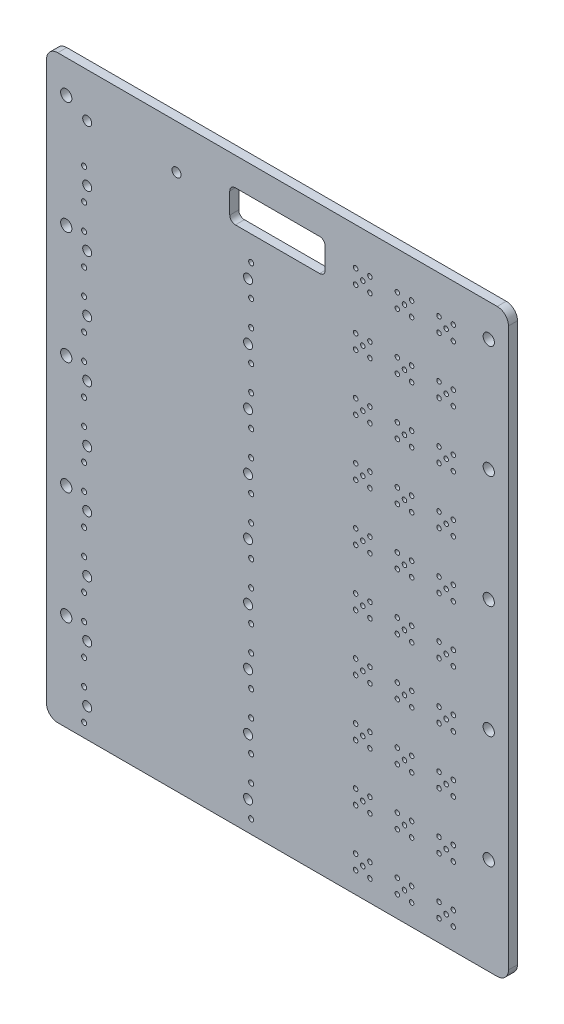
SolidWorks part; units mm, degrees
ref_plane "Front Plane" through (0, 0, 0) normal (0, 0, 1) x (1, 0, 0)
ref_plane "Top Plane" through (0, 0, 0) normal (0, 1, 0) x (1, 0, 0)
ref_plane "Right Plane" through (0, 0, 0) normal (1, 0, 0) x (0, 0, -1)
ref_plane "Plane4" through (0, 0, 0) normal (0, 0, -1) x (-1, 0, 0)
sketch "Sketch1" plane through (0, 0, 0) normal (0, 0, -1) x (-1, 0, 0)
  line L0 (7.475, 96.3) -> (-7.475, 96.3)
  line L1 (-8.475, 97.3) -> (-8.475, 101)
  line L2 (-7.475, 102) -> (7.475, 102)
  line L3 (8.475, 101) -> (8.475, 97.3)
  line L4 (39, 107) -> (-39, 107)
  line L5 (-41, 105) -> (-41, -105)
  line L6 (-39, -107) -> (39, -107)
  line L7 (41, -105) -> (41, 105)
  line L8 (8.475, -101) -> (8.475, -97.3)
  line L9 (-7.475, -102) -> (7.475, -102)
  line L10 (-8.475, -97.3) -> (-8.475, -101)
  line L11 (7.475, -96.3) -> (-7.475, -96.3)
  line L12 (41, -105) -> (41, -107) construction
  line L13 (41, -107) -> (39, -107) construction
  line L14 (41, 0) -> (-41, 0) construction
  line L15 (0, 107) -> (0, -107) construction
  arc A0 (8.475, 97.3) -> (7.475, 96.3) centre (7.475, 97.3) cw
  arc A1 (-7.475, 96.3) -> (-8.475, 97.3) centre (-7.475, 97.3) cw
  arc A2 (-8.475, 101) -> (-7.475, 102) centre (-7.475, 101) cw
  arc A3 (7.475, 102) -> (8.475, 101) centre (7.475, 101) cw
  circle A4 centre (34.325, -40.5) radius 0.45
  circle A5 centre (5.225, -43.25) radius 0.8
  circle A6 centre (-37.5, 21.2) radius 1
  circle A7 centre (5.225, -33.25) radius 0.8
  circle A8 centre (34.325, 46.5) radius 0.45
  circle A9 centre (33.775, -53.25) radius 0.8
  circle A10 centre (34.325, 82) radius 0.45
  circle A11 centre (4.675, 66.5) radius 0.45
  circle A12 centre (33.775, 19.25) radius 0.8
  circle A13 centre (4.675, -0.5) radius 0.45
  circle A14 centre (34.325, 26.5) radius 0.45
  circle A15 centre (5.225, -73.25) radius 0.8
  circle A16 centre (34.325, -66) radius 0.45
  circle A17 centre (5.225, 29.25) radius 0.8
  circle A18 centre (34.325, -80.5) radius 0.45
  circle A19 centre (34.325, 36.5) radius 0.45
  circle A20 centre (4.675, 22) radius 0.45
  circle A21 centre (33.775, -23.25) radius 0.8
  circle A22 centre (5.225, 19.25) radius 0.8
  circle A23 centre (33.775, -13.25) radius 0.8
  circle A24 centre (4.675, -10.5) radius 0.45
  circle A25 centre (34.325, 52) radius 0.45
  circle A26 centre (5.225, 89.25) radius 0.8
  circle A27 centre (5.225, -53.25) radius 0.8
  circle A28 centre (34.325, -70.5) radius 0.45
  circle A29 centre (34.325, -36) radius 0.45
  circle A30 centre (5.225, 59.25) radius 0.8
  circle A31 centre (33.775, 59.25) radius 0.8
  circle A32 centre (34.325, 32) radius 0.45
  circle A33 centre (33.775, -73.25) radius 0.8
  circle A34 centre (4.675, 46.5) radius 0.45
  circle A35 centre (4.675, 26.5) radius 0.45
  circle A36 centre (34.325, -6) radius 0.45
  circle A37 centre (34.325, -20.5) radius 0.45
  circle A38 centre (34.325, -60.5) radius 0.45
  circle A39 centre (5.225, -83.25) radius 0.8
  circle A40 centre (5.225, -13.25) radius 0.8
  circle A41 centre (33.775, -83.25) radius 0.8
  circle A42 centre (34.325, 92) radius 0.45
  circle A43 centre (33.775, -93.25) radius 0.8
  circle A44 centre (4.675, 32) radius 0.45
  circle A45 centre (4.675, 16.5) radius 0.45
  circle A46 centre (34.325, -50.5) radius 0.45
  circle A47 centre (4.675, 76.5) radius 0.45
  circle A48 centre (4.675, 82) radius 0.45
  circle A49 centre (34.325, 16.5) radius 0.45
  circle A50 centre (34.325, -56) radius 0.45
  circle A51 centre (5.225, -3.25) radius 0.8
  circle A52 centre (4.675, 36.5) radius 0.45
  circle A53 centre (4.675, -36) radius 0.45
  circle A54 centre (34.325, 86.5) radius 0.45
  circle A55 centre (33.775, 29.25) radius 0.8
  circle A56 centre (4.675, -26) radius 0.45
  circle A57 centre (4.675, -56) radius 0.45
  circle A58 centre (34.325, -30.5) radius 0.45
  circle A59 centre (33.775, 39.25) radius 0.8
  circle A60 centre (4.675, 56.5) radius 0.45
  circle A61 centre (34.325, 12) radius 0.45
  arc A62 (-39, 107) -> (-41, 105) centre (-39, 105) ccw
  arc A63 (-41, -105) -> (-39, -107) centre (-39, -105) ccw
  arc A64 (39, -107) -> (41, -105) centre (39, -105) ccw
  arc A65 (41, 105) -> (39, 107) centre (39, 105) ccw
  circle A66 centre (5.225, -63.25) radius 0.8
  circle A67 centre (4.675, -6) radius 0.45
  circle A68 centre (5.225, 49.25) radius 0.8
  circle A69 centre (4.675, -16) radius 0.45
  circle A70 centre (33.775, 9.25) radius 0.8
  circle A71 centre (4.675, -76) radius 0.45
  circle A72 centre (34.325, -76) radius 0.45
  circle A73 centre (4.675, -66) radius 0.45
  circle A74 centre (4.675, -30.5) radius 0.45
  circle A75 centre (34.325, 72) radius 0.45
  circle A76 centre (33.775, -63.25) radius 0.8
  circle A77 centre (33.775, 99.25) radius 0.8
  circle A78 centre (4.675, -86) radius 0.45
  circle A79 centre (4.675, 62) radius 0.45
  circle A80 centre (-37.5, 101.2) radius 1
  circle A81 centre (34.325, 76.5) radius 0.45
  circle A82 centre (4.675, -80.5) radius 0.45
  circle A83 centre (33.775, 49.25) radius 0.8
  circle A84 centre (4.675, 86.5) radius 0.45
  circle A85 centre (33.775, -33.25) radius 0.8
  circle A86 centre (4.675, 6.5) radius 0.45
  circle A87 centre (33.775, 79.25) radius 0.8
  circle A88 centre (34.325, -26) radius 0.45
  circle A89 centre (4.675, -60.5) radius 0.45
  circle A90 centre (4.675, 42) radius 0.45
  circle A91 centre (5.225, -23.25) radius 0.8
  circle A92 centre (34.325, 66.5) radius 0.45
  circle A93 centre (5.225, 79.25) radius 0.8
  circle A94 centre (4.675, -20.5) radius 0.45
  circle A95 centre (33.775, 89.25) radius 0.8
  circle A96 centre (17.925, -93.25) radius 0.8
  circle A97 centre (34.325, 22) radius 0.45
  circle A98 centre (4.675, 72) radius 0.45
  circle A99 centre (17.925, 99.25) radius 0.8
  circle A100 centre (4.675, 12) radius 0.45
  circle A101 centre (33.775, -3.25) radius 0.8
  circle A102 centre (34.325, 56.5) radius 0.45
  circle A103 centre (4.675, -70.5) radius 0.45
  circle A104 centre (34.325, -16) radius 0.45
  circle A105 centre (5.225, 39.25) radius 0.8
  circle A106 centre (34.325, -10.5) radius 0.45
  circle A107 centre (4.675, -50.5) radius 0.45
  circle A108 centre (-21.27, -2.0788) radius 0.4
  circle A109 centre (-31.21, -42.0789) radius 0.4
  circle A110 centre (-23.81, -44.6189) radius 0.4
  circle A111 centre (-15.14, -23.3489) radius 0.4
  circle A112 centre (-31.21, -44.6189) radius 0.4
  circle A114 centre (-16.41, -12.0788) radius 0.4
  circle A115 centre (-13.87, -24.6188) radius 0.4
  circle A116 centre (-21.27, -44.6189) radius 0.4
  circle A117 centre (-31.21, -4.6188) radius 0.4
  circle A118 centre (-15.14, -13.3489) radius 0.4
  circle A119 centre (-22.54, -13.3489) radius 0.4
  circle A120 centre (-31.21, -14.6189) radius 0.4
  circle A121 centre (-23.81, -22.0788) radius 0.4
  circle A122 centre (-29.94, -13.3489) radius 0.4
  circle A123 centre (-13.87, -12.0788) radius 0.4
  circle A124 centre (-28.67, -12.0788) radius 0.4
  circle A125 centre (-29.94, -43.3488) radius 0.4
  circle A126 centre (-22.54, -43.3488) radius 0.4
  circle A127 centre (-31.21, -2.0788) radius 0.4
  circle A128 centre (-23.81, -14.6189) radius 0.4
  circle A129 centre (-23.81, -12.0788) radius 0.4
  circle A130 centre (-16.41, -22.0788) radius 0.4
  circle A131 centre (-29.94, -3.3488) radius 0.4
  circle A132 centre (-21.27, -42.0789) radius 0.4
  circle A133 centre (-13.87, -14.6189) radius 0.4
  circle A134 centre (-15.14, -43.3488) radius 0.4
  circle A135 centre (-13.87, -42.0789) radius 0.4
  circle A136 centre (-16.41, -44.6189) radius 0.4
  circle A137 centre (-21.27, -24.6188) radius 0.4
  circle A138 centre (-23.81, -24.6188) radius 0.4
  circle A139 centre (-28.67, -4.6188) radius 0.4
  circle A140 centre (-16.41, -24.6188) radius 0.4
  circle A141 centre (-28.67, -44.6189) radius 0.4
  circle A142 centre (-21.27, -12.0788) radius 0.4
  circle A143 centre (-28.67, -42.0789) radius 0.4
  circle A144 centre (-13.87, -44.6189) radius 0.4
  circle A145 centre (-23.81, -42.0789) radius 0.4
  circle A146 centre (-28.67, -14.6189) radius 0.4
  circle A147 centre (-16.41, -42.0789) radius 0.4
  circle A148 centre (-31.21, -12.0788) radius 0.4
  circle A149 centre (-21.27, -14.6189) radius 0.4
  circle A150 centre (-13.87, -22.0788) radius 0.4
  circle A151 centre (-16.41, -14.6189) radius 0.4
  circle A152 centre (-22.54, -23.3489) radius 0.4
  circle A153 centre (-23.81, -2.0788) radius 0.4
  circle A154 centre (-23.81, -4.6188) radius 0.4
  circle A155 centre (-22.54, -3.3488) radius 0.4
  circle A156 centre (-21.27, -4.6188) radius 0.4
  circle A157 centre (-13.87, -2.0788) radius 0.4
  circle A158 centre (-16.41, -2.0788) radius 0.4
  circle A159 centre (-16.41, -4.6188) radius 0.4
  circle A160 centre (-15.14, -3.3488) radius 0.4
  circle A161 centre (-13.87, -4.6188) radius 0.4
  circle A162 centre (-28.67, -2.0788) radius 0.4
  circle A163 centre (-28.67, 10.4212) radius 0.4
  circle A164 centre (-31.21, 10.4212) radius 0.4
  circle A165 centre (-31.21, 7.8812) radius 0.4
  circle A166 centre (-29.94, 9.1512) radius 0.4
  circle A167 centre (-28.67, 7.8812) radius 0.4
  circle A168 centre (-21.27, 10.4212) radius 0.4
  circle A169 centre (-23.81, 10.4212) radius 0.4
  circle A170 centre (-23.81, 7.8812) radius 0.4
  circle A171 centre (-22.54, 9.1512) radius 0.4
  circle A172 centre (-21.27, 7.8812) radius 0.4
  circle A173 centre (-13.87, -54.6189) radius 0.4
  circle A174 centre (-15.14, -53.3489) radius 0.4
  circle A175 centre (-16.41, -54.6189) radius 0.4
  circle A176 centre (-16.41, -52.0789) radius 0.4
  circle A177 centre (-13.87, -52.0789) radius 0.4
  circle A178 centre (-21.27, -54.6189) radius 0.4
  circle A179 centre (-22.54, -53.3489) radius 0.4
  circle A180 centre (-23.81, -54.6189) radius 0.4
  circle A181 centre (-23.81, -52.0789) radius 0.4
  circle A182 centre (-21.27, -52.0789) radius 0.4
  circle A183 centre (-28.67, -54.6189) radius 0.4
  circle A184 centre (-29.94, -53.3489) radius 0.4
  circle A185 centre (-31.21, -54.6189) radius 0.4
  circle A186 centre (-31.21, -52.0789) radius 0.4
  circle A187 centre (-28.67, -52.0789) radius 0.4
  circle A188 centre (-13.87, 10.4212) radius 0.4
  circle A189 centre (-16.41, 10.4212) radius 0.4
  circle A190 centre (-16.41, 7.8812) radius 0.4
  circle A191 centre (-15.14, 9.1512) radius 0.4
  circle A192 centre (-13.87, 7.8812) radius 0.4
  circle A193 centre (-28.67, 20.4212) radius 0.4
  circle A194 centre (-31.21, 20.4212) radius 0.4
  circle A195 centre (-31.21, 17.8812) radius 0.4
  circle A196 centre (-29.94, 19.1512) radius 0.4
  circle A197 centre (-28.67, 17.8812) radius 0.4
  circle A198 centre (-21.27, 20.4212) radius 0.4
  circle A199 centre (-23.81, 20.4212) radius 0.4
  circle A200 centre (-23.81, 17.8812) radius 0.4
  circle A201 centre (-22.54, 19.1512) radius 0.4
  circle A202 centre (-21.27, 17.8812) radius 0.4
  circle A203 centre (-13.87, 20.4212) radius 0.4
  circle A204 centre (-16.41, 20.4212) radius 0.4
  circle A205 centre (-16.41, 17.8812) radius 0.4
  circle A206 centre (-15.14, 19.1512) radius 0.4
  circle A207 centre (-13.87, 17.8812) radius 0.4
  circle A208 centre (-28.67, 30.4212) radius 0.4
  circle A209 centre (-31.21, 30.4212) radius 0.4
  circle A210 centre (-31.21, 27.8812) radius 0.4
  circle A211 centre (-29.94, 29.1512) radius 0.4
  circle A212 centre (-28.67, 27.8812) radius 0.4
  circle A213 centre (-21.27, 30.4212) radius 0.4
  circle A214 centre (-23.81, 30.4212) radius 0.4
  circle A215 centre (-23.81, 27.8812) radius 0.4
  circle A216 centre (-22.54, 29.1512) radius 0.4
  circle A217 centre (-21.27, 27.8812) radius 0.4
  circle A218 centre (-13.87, 30.4212) radius 0.4
  circle A219 centre (-16.41, 30.4212) radius 0.4
  circle A220 centre (-16.41, 27.8812) radius 0.4
  circle A221 centre (-15.14, 29.1512) radius 0.4
  circle A222 centre (-13.87, 27.8812) radius 0.4
  circle A223 centre (-28.67, 40.4211) radius 0.4
  circle A224 centre (-31.21, 40.4211) radius 0.4
  circle A225 centre (-31.21, 37.8812) radius 0.4
  circle A226 centre (-29.94, 39.1512) radius 0.4
  circle A227 centre (-28.67, 37.8812) radius 0.4
  circle A228 centre (-13.87, -64.6188) radius 0.4
  circle A229 centre (-15.14, -63.3488) radius 0.4
  circle A230 centre (-16.41, -64.6188) radius 0.4
  circle A231 centre (-16.41, -62.0789) radius 0.4
  circle A232 centre (-13.87, -62.0789) radius 0.4
  circle A233 centre (-21.27, -64.6188) radius 0.4
  circle A234 centre (-22.54, -63.3488) radius 0.4
  circle A235 centre (-23.81, -64.6188) radius 0.4
  circle A236 centre (-23.81, -62.0789) radius 0.4
  circle A237 centre (-21.27, -62.0789) radius 0.4
  circle A238 centre (-28.67, -64.6188) radius 0.4
  circle A239 centre (-29.94, -63.3488) radius 0.4
  circle A240 centre (-31.21, -64.6188) radius 0.4
  circle A241 centre (-31.21, -62.0789) radius 0.4
  circle A242 centre (-28.67, -62.0789) radius 0.4
  circle A243 centre (-21.27, 40.4211) radius 0.4
  circle A244 centre (-23.81, 40.4211) radius 0.4
  circle A245 centre (-23.81, 37.8812) radius 0.4
  circle A246 centre (-22.54, 39.1512) radius 0.4
  circle A247 centre (-21.27, 37.8812) radius 0.4
  circle A248 centre (-13.87, 40.4211) radius 0.4
  circle A249 centre (-16.41, 40.4211) radius 0.4
  circle A250 centre (-16.41, 37.8812) radius 0.4
  circle A251 centre (-15.14, 39.1512) radius 0.4
  circle A252 centre (-13.87, 37.8812) radius 0.4
  circle A253 centre (-28.67, 50.4211) radius 0.4
  circle A254 centre (-31.21, 50.4211) radius 0.4
  circle A255 centre (-31.21, 47.8811) radius 0.4
  circle A256 centre (-29.94, 49.1512) radius 0.4
  circle A257 centre (-28.67, 47.8811) radius 0.4
  circle A258 centre (-21.27, 50.4211) radius 0.4
  circle A259 centre (-23.81, 50.4211) radius 0.4
  circle A260 centre (-23.81, 47.8811) radius 0.4
  circle A261 centre (-22.54, 49.1512) radius 0.4
  circle A262 centre (-21.27, 47.8811) radius 0.4
  circle A263 centre (-13.87, 50.4211) radius 0.4
  circle A264 centre (-16.41, 50.4211) radius 0.4
  circle A265 centre (-16.41, 47.8811) radius 0.4
  circle A266 centre (-15.14, 49.1512) radius 0.4
  circle A267 centre (-13.87, 47.8811) radius 0.4
  circle A268 centre (-28.67, 60.4211) radius 0.4
  circle A269 centre (-31.21, 60.4211) radius 0.4
  circle A270 centre (-31.21, 57.8811) radius 0.4
  circle A271 centre (-29.94, 59.1512) radius 0.4
  circle A272 centre (-28.67, 57.8811) radius 0.4
  circle A273 centre (-21.27, 60.4211) radius 0.4
  circle A274 centre (-23.81, 60.4211) radius 0.4
  circle A275 centre (-23.81, 57.8811) radius 0.4
  circle A276 centre (-22.54, 59.1512) radius 0.4
  circle A277 centre (-21.27, 57.8811) radius 0.4
  circle A278 centre (-13.87, 60.4211) radius 0.4
  circle A279 centre (-16.41, 60.4211) radius 0.4
  circle A280 centre (-16.41, 57.8811) radius 0.4
  circle A281 centre (-15.14, 59.1512) radius 0.4
  circle A282 centre (-13.87, 57.8811) radius 0.4
  circle A283 centre (-13.87, -74.6188) radius 0.4
  circle A284 centre (-15.14, -73.3489) radius 0.4
  circle A285 centre (-16.41, -74.6188) radius 0.4
  circle A286 centre (-16.41, -72.0789) radius 0.4
  circle A287 centre (-13.87, -72.0789) radius 0.4
  circle A288 centre (-21.27, -74.6188) radius 0.4
  circle A289 centre (-22.54, -73.3489) radius 0.4
  circle A290 centre (-23.81, -74.6188) radius 0.4
  circle A291 centre (-23.81, -72.0789) radius 0.4
  circle A292 centre (-21.27, -72.0789) radius 0.4
  circle A293 centre (-28.67, -74.6188) radius 0.4
  circle A294 centre (-29.94, -73.3489) radius 0.4
  circle A295 centre (-31.21, -74.6188) radius 0.4
  circle A296 centre (-31.21, -72.0789) radius 0.4
  circle A297 centre (-28.67, -72.0789) radius 0.4
  circle A298 centre (-28.67, 70.4211) radius 0.4
  circle A299 centre (-31.21, 70.4211) radius 0.4
  circle A300 centre (-31.21, 67.8812) radius 0.4
  circle A301 centre (-29.94, 69.1512) radius 0.4
  circle A302 centre (-28.67, 67.8812) radius 0.4
  circle A303 centre (-21.27, 70.4211) radius 0.4
  circle A304 centre (-23.81, 70.4211) radius 0.4
  circle A305 centre (-23.81, 67.8812) radius 0.4
  circle A306 centre (-22.54, 69.1512) radius 0.4
  circle A307 centre (-21.27, 67.8812) radius 0.4
  circle A308 centre (-13.87, 70.4211) radius 0.4
  circle A309 centre (-16.41, 70.4211) radius 0.4
  circle A310 centre (-16.41, 67.8812) radius 0.4
  circle A311 centre (-15.14, 69.1512) radius 0.4
  circle A312 centre (-13.87, 67.8812) radius 0.4
  circle A313 centre (-28.67, 80.4211) radius 0.4
  circle A314 centre (-31.21, 80.4211) radius 0.4
  circle A315 centre (-31.21, 77.8812) radius 0.4
  circle A316 centre (-29.94, 79.1512) radius 0.4
  circle A317 centre (-28.67, 77.8812) radius 0.4
  circle A318 centre (-21.27, 80.4211) radius 0.4
  circle A319 centre (-23.81, 80.4211) radius 0.4
  circle A320 centre (-23.81, 77.8812) radius 0.4
  circle A321 centre (-22.54, 79.1512) radius 0.4
  circle A322 centre (-21.27, 77.8812) radius 0.4
  circle A323 centre (-13.87, 80.4211) radius 0.4
  circle A324 centre (-16.41, 80.4211) radius 0.4
  circle A325 centre (-16.41, 77.8812) radius 0.4
  circle A326 centre (-15.14, 79.1512) radius 0.4
  circle A327 centre (-13.87, 77.8812) radius 0.4
  circle A328 centre (-28.67, 90.4212) radius 0.4
  circle A329 centre (-31.21, 90.4212) radius 0.4
  circle A330 centre (-31.21, 87.8812) radius 0.4
  circle A331 centre (-29.94, 89.1512) radius 0.4
  circle A332 centre (-28.67, 87.8812) radius 0.4
  circle A333 centre (-21.27, 90.4212) radius 0.4
  circle A334 centre (-23.81, 90.4212) radius 0.4
  circle A335 centre (-23.81, 87.8812) radius 0.4
  circle A336 centre (-22.54, 89.1512) radius 0.4
  circle A337 centre (-21.27, 87.8812) radius 0.4
  circle A338 centre (-13.87, -84.6188) radius 0.4
  circle A339 centre (-15.14, -83.3488) radius 0.4
  circle A340 centre (-16.41, -84.6188) radius 0.4
  circle A341 centre (-16.41, -82.0789) radius 0.4
  circle A342 centre (-13.87, -82.0789) radius 0.4
  circle A343 centre (-21.27, -84.6188) radius 0.4
  circle A344 centre (-22.54, -83.3488) radius 0.4
  circle A345 centre (-23.81, -84.6188) radius 0.4
  circle A346 centre (-23.81, -82.0789) radius 0.4
  circle A347 centre (-21.27, -82.0789) radius 0.4
  circle A348 centre (-28.67, -84.6188) radius 0.4
  circle A349 centre (-29.94, -83.3488) radius 0.4
  circle A350 centre (-31.21, -84.6188) radius 0.4
  circle A351 centre (-31.21, -82.0789) radius 0.4
  circle A352 centre (-28.67, -82.0789) radius 0.4
  circle A353 centre (-13.87, 90.4212) radius 0.4
  circle A354 centre (-16.41, 90.4212) radius 0.4
  circle A355 centre (-16.41, 87.8812) radius 0.4
  circle A356 centre (-15.14, 89.1512) radius 0.4
  circle A357 centre (-13.87, 87.8812) radius 0.4
  circle A358 centre (4.675, -40.5) radius 0.45
  circle A359 centre (34.325, -46) radius 0.45
  circle A360 centre (34.325, 6.5) radius 0.45
  circle A361 centre (4.675, 92) radius 0.45
  circle A362 centre (34.325, 62) radius 0.45
  circle A363 centre (34.325, -86) radius 0.45
  circle A364 centre (4.675, -46) radius 0.45
  circle A365 centre (34.325, 42) radius 0.45
  circle A366 centre (5.225, 69.25) radius 0.8
  circle A367 centre (33.775, 69.25) radius 0.8
  circle A368 centre (33.775, -43.25) radius 0.8
  circle A369 centre (5.225, 9.25) radius 0.8
  circle A370 centre (4.675, 52) radius 0.45
  circle A371 centre (34.325, -0.5) radius 0.45
  circle A372 centre (-13.87, -92.0789) radius 0.4
  circle A373 centre (-31.21, -94.6188) radius 0.4
  circle A374 centre (-28.67, -92.0789) radius 0.4
  circle A375 centre (-28.67, -94.6188) radius 0.4
  circle A376 centre (-29.94, -93.3488) radius 0.4
  circle A377 centre (-23.81, -92.0789) radius 0.4
  circle A378 centre (-16.41, -94.6188) radius 0.4
  circle A379 centre (-21.27, -94.6188) radius 0.4
  circle A380 centre (-21.27, -92.0789) radius 0.4
  circle A381 centre (-23.81, -94.6188) radius 0.4
  circle A382 centre (-16.41, -92.0789) radius 0.4
  circle A383 centre (-31.21, -92.0789) radius 0.4
  circle A384 centre (-22.54, -93.3488) radius 0.4
  circle A385 centre (-13.87, -94.6188) radius 0.4
  circle A386 centre (-15.14, -93.3488) radius 0.4
  circle A387 centre (-21.27, -22.0788) radius 0.4
  circle A388 centre (-28.67, -24.6188) radius 0.4
  circle A389 centre (-29.94, -23.3489) radius 0.4
  circle A390 centre (-31.21, -24.6188) radius 0.4
  circle A391 centre (-31.21, -22.0788) radius 0.4
  circle A392 centre (-28.67, -22.0788) radius 0.4
  circle A393 centre (-13.87, -34.6189) radius 0.4
  circle A394 centre (-15.14, -33.3488) radius 0.4
  circle A395 centre (-16.41, -34.6189) radius 0.4
  circle A396 centre (-16.41, -32.0789) radius 0.4
  circle A397 centre (-13.87, -32.0789) radius 0.4
  circle A398 centre (-21.27, -34.6189) radius 0.4
  circle A399 centre (-22.54, -33.3488) radius 0.4
  circle A400 centre (-23.81, -34.6189) radius 0.4
  circle A401 centre (-23.81, -32.0789) radius 0.4
  circle A402 centre (-21.27, -32.0789) radius 0.4
  circle A403 centre (-28.67, -34.6189) radius 0.4
  circle A404 centre (-29.94, -33.3488) radius 0.4
  circle A405 centre (-31.21, -34.6189) radius 0.4
  circle A406 centre (-31.21, -32.0789) radius 0.4
  circle A407 centre (-28.67, -32.0789) radius 0.4
  circle A408 centre (-37.5, -81.2) radius 1
  circle A409 centre (37.5, 81.2) radius 1
  circle A412 centre (-37.5, 41.2) radius 1
  circle A413 centre (-37.5, -41.2) radius 1
  circle A414 centre (-37.5, -101.2) radius 1
  circle A415 centre (-37.5, 61.2) radius 1
  circle A416 centre (37.5, 61.2) radius 1
  circle A417 centre (-37.5, 81.2) radius 1
  circle A420 centre (-37.5, -61.2) radius 1
  circle A421 centre (37.5, 41.2) radius 1
  circle A422 centre (-37.5, -21.2) radius 1
  circle A423 centre (37.5, 101.2) radius 1
  circle A424 centre (37.5, 21.2) radius 1
  arc A425 (8.475, -97.3) -> (7.475, -96.3) centre (7.475, -97.3) ccw
  arc A426 (7.475, -102) -> (8.475, -101) centre (7.475, -101) ccw
  arc A427 (-8.475, -101) -> (-7.475, -102) centre (-7.475, -101) ccw
  arc A428 (-7.475, -96.3) -> (-8.475, -97.3) centre (-7.475, -97.3) ccw
  point P876 (0, 102)
  dimension "D3" = 2
  dimension "D4" = 1
  dimension "D9" = 2
  dimension "D1" = 82
  dimension "D2" = 214
  dimension "D5" = 16.95
  dimension "D6" = 5.7
  dimension "D7" = 5
  dimension "D8" = 5
  dimension "D10" = 5.8
  dimension "D11" = 3.5
  dimension "D12" = 20
extrude "Boss-Extrude1" [suppressed] add sketch "Sketch1" against normal blind 1.5
sketch "Sketch2" plane through (0, 0, 0) normal (0, 0, 1) x (1, 0, 0)
  line L0 (82, 103) -> (0, 103)
  line L1 (0, 103) -> (0, 0)
  line L2 (0, 0) -> (82, 0)
  line L3 (82, 0) -> (82, 103)
  dimension "D1" = 82
  dimension "D2" = 103
extrude "mainBoard" add sketch "Sketch2" along normal blind 1.6
ref_plane "X_mirror" through (41, 0, 0) normal (-1, 0, 0) x (0, 0, 1)
sketch "Sketch3" plane through (0, 0, 1.6) normal (0, 0, 1) x (1, 0, 0)
  line L0 (82, 103) -> (0, 103) construction
  line L1 (41, 103) -> (41, 0) construction
  line L2 (0, 0) -> (82, 0) construction
  line L5 (32.525, 98) -> (49.475, 98)
  line L6 (32.525, 98) -> (32.525, 92.3)
  line L7 (32.525, 92.3) -> (49.475, 92.3)
  line L8 (49.475, 98) -> (49.475, 92.3)
  point P6 (41, 98)
  dimension "D1" = 5
  dimension "D3" = 16.95
  dimension "D4" = 5.7
extrude "solarHole" cut sketch "Sketch3" against normal through all
fillet "Fillet1" radius 2 4 edges at (0, 0, 0.8) (82, 0, 0.8) (82, 103, 0.8) (0, 103, 0.8)
fillet "Fillet2" radius 1 4 edges at (49.475, 92.3, 0.8) (49.475, 98, 0.8) (32.525, 92.3, 0.8) (32.525, 98, 0.8)
hole_wizard "Ø2.0mm Hole_screw" positions "Sketch4" profile "Sketch5" hole size "Ø2.0" standard "ANSI Metric"
sketch "Sketch4" plane through (0, 0, 1.6) normal (0, 0, 1) x (1, 0, 0)
  line L0 (80, 103) -> (2, 103) construction
  line L1 (0, 101) -> (0, 2) construction
  point P0 (3.5, 97.2)
  dimension "D1" = 5.8
  dimension "D2" = 3.5
sketch "Sketch5" plane through (3.5, 97.2, 1.6) normal (1, 0, 0) x (0, -1, 0)
  line L0 (0, 0) -> (0, 10.1259)
  line L1 (0, 10.1259) -> (1, 9.525)
  line L2 (1, 9.525) -> (1, 0)
  line L5 (1, 0) -> (0, 0)
  line L10 (0, 10.1259) -> (-1, 9.525) construction
  line L11 (0, -6.35) -> (0, 107.95) construction
  dimension "Hole Dia." = 2
  dimension "Hole Depth" = 9.525
  dimension "Drill Angle" = 118
hole_wizard "Ø1.6mm Hole_20pin" positions "Sketch12" profile "Sketch13" hole size "Ø1.5" standard "ANSI Metric"
sketch "Sketch12" plane through (0, 0, 1.6) normal (0, 0, 1) x (1, 0, 0)
  line L0 (80, 103) -> (2, 103) construction
  line L1 (0, 101) -> (0, 2) construction
  point P0 (7.225, 95.15)
  point P2 (23.075, 95.15)
  dimension "D1" = 15.85
  dimension "D2" = 7.85
  dimension "D3" = 7.225
sketch "Sketch13" plane through (7.225, 95.15, 1.6) normal (1, 0, 0) x (0, -1, 0)
  line L0 (0, 0) -> (0, 10.0057)
  line L1 (0, 10.0057) -> (0.8, 9.525)
  line L2 (0.8, 9.525) -> (0.8, 0)
  line L5 (0.8, 0) -> (0, 0)
  line L10 (0, 10.0057) -> (-0.8, 9.525) construction
  line L11 (0, -6.35) -> (0, 107.95) construction
  dimension "Hole Dia." = 1.6
  dimension "Hole Depth" = 9.525
  dimension "Drill Angle" = 118
hole_wizard "Ø1.6mm Hole_40pn_big" positions "Sketch6" profile "Sketch7" hole size "Ø1.5" standard "ANSI Metric"
sketch "Sketch6" plane through (0, 0, 1.6) normal (0, 0, 1) x (1, 0, 0)
  line L0 (0, 101) -> (0, 2) construction
  line L1 (80, 103) -> (2, 103) construction
  point P14 (7.225, 85.15)
  point P16 (35.775, 85.15)
  dimension "D1" = 7.225
  dimension "D7" = 17.85
  dimension "D8" = 28.55
sketch "Sketch7" plane through (7.225, 85.15, 1.6) normal (1, 0, 0) x (0, -1, 0)
  line L0 (0, 0) -> (0, 10.0057)
  line L1 (0, 10.0057) -> (0.8, 9.525)
  line L2 (0.8, 9.525) -> (0.8, 0)
  line L5 (0.8, 0) -> (0, 0)
  line L10 (0, 10.0057) -> (-0.8, 9.525) construction
  line L11 (0, -6.35) -> (0, 107.95) construction
  dimension "Hole Dia." = 1.6
  dimension "Hole Depth" = 9.525
  dimension "Drill Angle" = 118
hole_wizard "Ø0.9mm Hole_40pin_tiny" positions "Sketch10" profile "Sketch11" hole size "Ø1.5" standard "ANSI Metric"
sketch "Sketch10" plane through (0, 0, 1.6) normal (0, 0, 1) x (1, 0, 0)
  line L1 (7.225, 85.15) -> (35.775, 85.15) construction
  line L3 (21.5, -11.0236) -> (21.5, 181.3236) construction
  circle A0 centre (7.225, 85.15) radius 0.8 construction
  point P0 (6.675, 87.9)
  point P24 (21.5, 85.15)
  point P25 (21.5, 85.15)
  point P27 (6.675, 82.4)
  point P29 (36.325, 87.9)
  point P30 (36.325, 82.4)
  dimension "D1" = 0.55
  dimension "D2" = 5.5
sketch "Sketch11" plane through (6.675, 87.9, 1.6) normal (1, 0, 0) x (0, -1, 0)
  line L0 (0, 0) -> (0, 9.7954)
  line L1 (0, 9.7954) -> (0.45, 9.525)
  line L2 (0.45, 9.525) -> (0.45, 0)
  line L5 (0.45, 0) -> (0, 0)
  line L10 (0, 9.7954) -> (-0.45, 9.525) construction
  line L11 (0, -6.35) -> (0, 107.95) construction
  dimension "Hole Dia." = 0.9
  dimension "Hole Depth" = 9.525
  dimension "Drill Angle" = 118
hole_wizard "Ø0.8mm MMCX Hole" positions "Sketch8" profile "Sketch9" hole size "Ø1.0" standard "ANSI Metric"
sketch "Sketch8" plane through (0, 0, 1.6) normal (0, 0, 1) x (1, 0, 0)
  line L0 (69.67, 86.32) -> (72.21, 83.78) construction
  line L2 (80, 103) -> (2, 103) construction
  line L3 (82, 2) -> (82, 101) construction
  point P0 (70.94, 85.05)
  point P2 (69.67, 86.32)
  point P4 (72.21, 86.32)
  point P6 (72.21, 83.78)
  point P8 (69.67, 83.78)
  point P21 (70.94, 85.05)
  dimension "D1" = 2.54
  dimension "D2" = 2.54
  dimension "D3" = 17.95
  dimension "D4" = 11.06
sketch "Sketch9" plane through (70.94, 85.05, 1.6) normal (1, 0, 0) x (0, -1, 0)
  line L0 (0, 0) -> (0, 9.7653)
  line L1 (0, 9.7653) -> (0.4, 9.525)
  line L2 (0.4, 9.525) -> (0.4, 0)
  line L5 (0.4, 0) -> (0, 0)
  line L10 (0, 9.7653) -> (-0.4, 9.525) construction
  line L11 (0, -6.35) -> (0, 107.95) construction
  dimension "Hole Dia." = 0.8
  dimension "Hole Depth" = 9.525
  dimension "Drill Angle" = 118
pattern_linear "MMCX_intra-card" count 3 spacing 7.4 along (-1, 0, 0) of "Ø0.8mm MMCX Hole"
pattern_linear "Zpos_block" count 9 spacing 10 along (0, -1, 0) of "MMCX_intra-card", "Ø0.9mm Hole_40pin_tiny", "Ø1.6mm Hole_40pn_big", "Ø0.8mm MMCX Hole"
pattern_linear "Zpos_antennaMMCX" count 2 spacing 10 along (0, 1, 0) of "MMCX_intra-card", "Ø0.8mm MMCX Hole"
pattern_linear "screwHoles_intra-rail" count 5 spacing 20 along (0, -1, 0) of "Ø2.0mm Hole_screw"
pattern_linear "Zneg_block" [suppressed] count 2 spacing 92.4
pattern_linear "Zneg_antennaMMCX" [suppressed] count 3 spacing 10
ref_plane "Y_mirror" through (0, 51.5, 0) normal (0, 1, 0) x (1, 0, 0)
mirror "screwHoles_trans-rail" about plane through (41, 0, 0) normal (-1, 0, 0) of "Ø2.0mm Hole_screw", "screwHoles_intra-rail"
mirror "screwHoles_Zneg_block" [suppressed] about plane through (0, 51.5, 0) normal (0, 1, 0)
